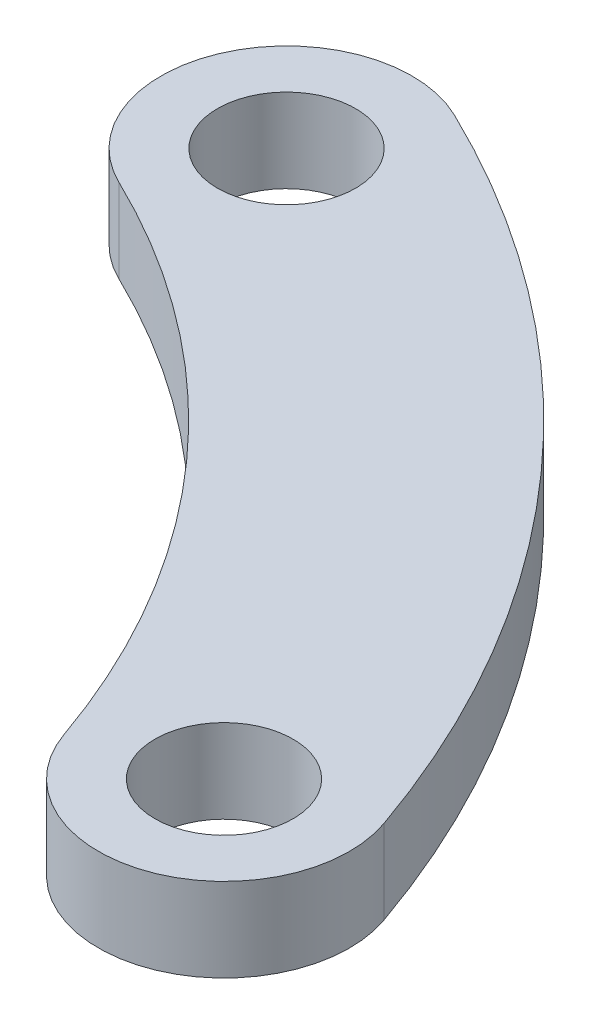
SolidWorks part; units mm, degrees
ref_plane "Front Plane" through (0, 0, 0) normal (0, 0, 1) x (1, 0, 0)
ref_plane "Top Plane" through (0, 0, 0) normal (0, 1, 0) x (1, 0, 0)
ref_plane "Right Plane" through (0, 0, 0) normal (1, 0, 0) x (0, 0, -1)
sketch "Sketch1" plane through (0, 2, 0) normal (0, 1, 0) x (1, 0, 0)
  line L0 (0, 0) -> (22.8034, 7.9515) construction
  line L1 (0, 0) -> (10.5019, 21.747) construction
  circle A10 centre (0, 0) radius 24.15 construction
  arc A12 (10.5019, 21.747) -> (22.8034, 7.9515) centre (0, 0) cw construction
  arc A13 (25.6362, 8.9392) -> (11.8065, 24.4485) centre (0, 0) ccw
  arc A14 (19.9707, 6.9637) -> (9.1973, 19.0455) centre (0, 0) ccw
  arc A15 (19.9707, 6.9637) -> (25.6362, 8.9392) centre (22.8034, 7.9515) ccw
  arc A16 (11.8065, 24.4485) -> (9.1973, 19.0455) centre (10.5019, 21.747) ccw
  circle A17 centre (10.5019, 21.747) radius 1.65
  circle A18 centre (22.8034, 7.9515) radius 1.65
  point P16 (18.0247, 16.0727)
  dimension "D1" = 48.3
  dimension "D2" = 45
  dimension "D3" = 3
  dimension "D4" = 3.3
  dimension "D5" = 3.3
extrude "Boss-Extrude1" add sketch "Sketch1" along normal blind 2
